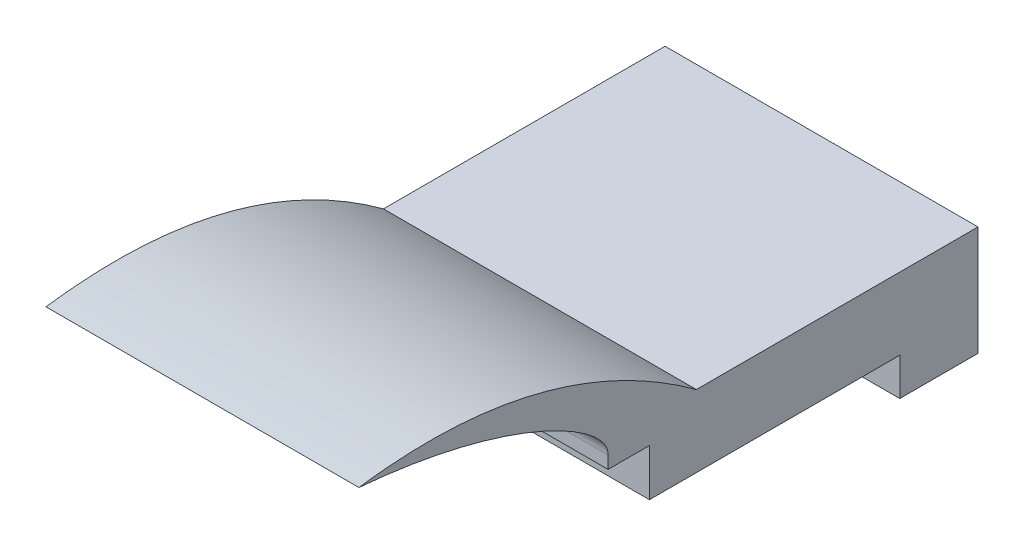
SolidWorks part; units mm, degrees
material "ABS"
ref_plane "Front Plane" through (0, 0, 0) normal (0, 0, 1) x (1, 0, 0)
ref_plane "Top Plane" through (0, 0, 0) normal (0, 1, 0) x (1, 0, 0)
ref_plane "Right Plane" through (0, 0, 0) normal (1, 0, 0) x (0, 0, -1)
curve "Curve1"
  spline degree 3 poles (0, 0.0012, 1.0003) (0, 0.0015, 0.9994) (0, 0.0028, 0.9958) (0, 0.0055, 0.9879) (0, 0.0099, 0.9747) (0, 0.0159, 0.9565) (0, 0.0233, 0.9333) (0, 0.0318, 0.9054) (0, 0.0411, 0.8731) (0, 0.051, 0.8366) (0, 0.0612, 0.7964) (0, 0.0713, 0.7528) (0, 0.0811, 0.7063) (0, 0.0903, 0.6574) (0, 0.0985, 0.6067) (0, 0.1057, 0.5546) (0, 0.1115, 0.5018) (0, 0.1158, 0.4488) (0, 0.1186, 0.3959) (0, 0.1189, 0.3436) (0, 0.1164, 0.2927) (0, 0.1112, 0.2442) (0, 0.1037, 0.1988) (0, 0.0942, 0.157) (0, 0.0831, 0.1194) (0, 0.0711, 0.0865) (0, 0.0584, 0.0585) (0, 0.0457, 0.0357) (0, 0.0334, 0.0184) (0, 0.0218, 0.0064) (0, 0.0108, -0.0005) (0, -0.0003, -0.0011) (0, -0.0092, 0.0055) (0, -0.0148, 0.017) (0, -0.0185, 0.0329) (0, -0.0204, 0.0533) (0, -0.0208, 0.0781) (0, -0.0198, 0.107) (0, -0.0176, 0.1398) (0, -0.0147, 0.176) (0, -0.0111, 0.2153) (0, -0.0074, 0.2574) (0, -0.0037, 0.3019) (0, -0.0005, 0.3484) (0, 0.002, 0.397) (0, 0.0037, 0.4471) (0, 0.0055, 0.4983) (0, 0.0069, 0.5496) (0, 0.0079, 0.6006) (0, 0.0085, 0.6505) (0, 0.0086, 0.699) (0, 0.0083, 0.7455) (0, 0.0076, 0.7894) (0, 0.0065, 0.8302) (0, 0.0053, 0.8675) (0, 0.0039, 0.9007) (0, 0.0027, 0.9296) (0, 0.0013, 0.9539) (0, 0.0006, 0.9727) (0, -0.0011, 0.9872) (0, 0, 0.9944) (0, -0.002, 0.9999) (0, -0.0005, 1) (0, 0, 1) knots 0 0 0 0 0.001372 0.005465 0.012235 0.021602 0.033461 0.047671 0.064081 0.082496 0.102719 0.124527 0.147676 0.171913 0.196978 0.222597 0.248497 0.274385 0.300041 0.32569 0.350525 0.37428 0.396711 0.417577 0.436654 0.453744 0.46868 0.481329 0.491631 0.499616 0.505546 0.510185 0.514824 0.520702 0.528516 0.538466 0.550543 0.564643 0.580638 0.598345 0.617584 0.638174 0.659922 0.682632 0.706121 0.730727 0.7557 0.780732 0.805564 0.829932 0.85357 0.876213 0.89761 0.917519 0.935698 0.951943 0.966047 0.97784 0.987174 0.993932 0.998018 0.999386 1 1 1 1
sketch "Sketch1" plane through (0, 0, 0) normal (1, 0, 0) x (0, 0, -1)
  line L1 (12.2165, 4.064) -> (12.2165, -1.016)
  line L3 (48.0533, 9.144) -> (48.0533, -35.306)
  line L4 (48.0533, -35.306) -> (29.0033, -35.306)
  line L5 (29.0033, -35.306) -> (29.0033, -1.016)
  line L6 (29.0033, -1.016) -> (12.2165, -1.016)
  line L8 (69.85, 0) -> (-69.85, 0) construction
  line L10 (0, 45.8699) -> (0, -45.8699) construction
  spline S0 degree 2 poles (-88.9, 43.18) (-12.9539, 53.7771) (48.0533, 9.144) knots 0 0 0 1 1 1
  spline S1 degree 3 poles (-88.9, 43.18) (-83.9463, 42.757) (-73.5905, 41.6218) (-58.3096, 39.1178) (-43.5398, 35.7782) (-30.2487, 31.895) (-18.5919, 27.6429) (-8.6949, 23.1943) (-0.6517, 18.7211) (5.5019, 14.3816) (9.7327, 10.2704) (11.8983, 6.8093) (12.2184, 4.6962) (12.2165, 4.064) knots 0.353791 0.353791 0.353791 0.353791 0.37428 0.396711 0.417577 0.436654 0.453744 0.46868 0.481329 0.491631 0.499616 0.505546 0.508115 0.508115 0.508115 0.508115
  dimension "D2" = 4.064
  dimension "D3" = 5.08
  dimension "D5" = 88.9
  dimension "D6" = 36.195
  dimension "D7" = 44.45
  dimension "D8" = 34.29
  dimension "D9" = 19.05
  dimension "D10" = 38.1
  dimension "D11" = 9.7768
  dimension "D12" = 48.0533
  dimension "D14" = 43.18
extrude "Boss-Extrude1" add sketch "Sketch1" along normal mid plane 127
sketch "Sketch2" plane through (0, 0, -48.0533) normal (0, 0, -1) x (-1, 0, 0)
  line L0 (-63.5, -11.176) -> (-31.75, -11.176) construction
  line L1 (-63.5, -35.306) -> (-63.5, 9.144) construction
  line L2 (-31.75, -11.176) -> (31.75, -11.176) construction
  line L3 (31.75, -11.176) -> (63.5, -11.176) construction
  line L4 (63.5, -35.306) -> (63.5, 9.144) construction
  line L5 (-63.5, 9.144) -> (63.5, 9.144) construction
  circle A0 centre (-31.75, -11.176) radius 3.175
  circle A1 centre (31.75, -11.176) radius 3.175
  dimension "D1" = 6.35
  dimension "D2" = 63.5
  dimension "D3" = 20.32
extrude "Cut-Extrude1" cut sketch "Sketch2" against normal through all both and the other way through all
sketch "Sketch3" plane through (0, 0, -48.0533) normal (0, 0, -1) x (-1, 0, 0)
  line L4 (63.5, -35.306) -> (63.5, 9.144)
  line L5 (63.5, 9.144) -> (-63.5, 9.144)
  line L6 (-63.5, 9.144) -> (-63.5, -35.306)
  line L7 (-63.5, -35.306) -> (63.5, -35.306)
  line L8 (63.5, -35.306) -> (63.5, 9.144)
  line L9 (63.5, 9.144) -> (-63.5, 9.144)
  line L10 (-63.5, 9.144) -> (-63.5, -35.306)
  line L11 (-63.5, -35.306) -> (63.5, -35.306)
  circle A0 centre (-31.75, -11.176) radius 3.175 construction
  circle A1 centre (-31.75, -11.176) radius 3.175
  circle A2 centre (31.75, -11.176) radius 3.175 construction
  circle A3 centre (31.75, -11.176) radius 3.175
  dimension "D1" = 0
extrude "Boss-Extrude2" add sketch "Sketch3" along normal blind 114.3
sketch "Sketch4" plane through (-63.5, 0, 0) normal (-1, 0, 0) x (0, 0, 1)
  line L1 (-29.0033, -35.306) -> (-130.6033, -35.306)
  line L2 (-29.0033, -35.306) -> (-29.0033, -20.066)
  line L3 (-29.0033, -20.066) -> (-130.6033, -20.066)
  line L4 (-130.6033, -35.306) -> (-130.6033, -20.066)
  dimension "D1" = 101.6
  dimension "D2" = 15.24
extrude "Cut-Extrude2" cut sketch "Sketch4" against normal through all
